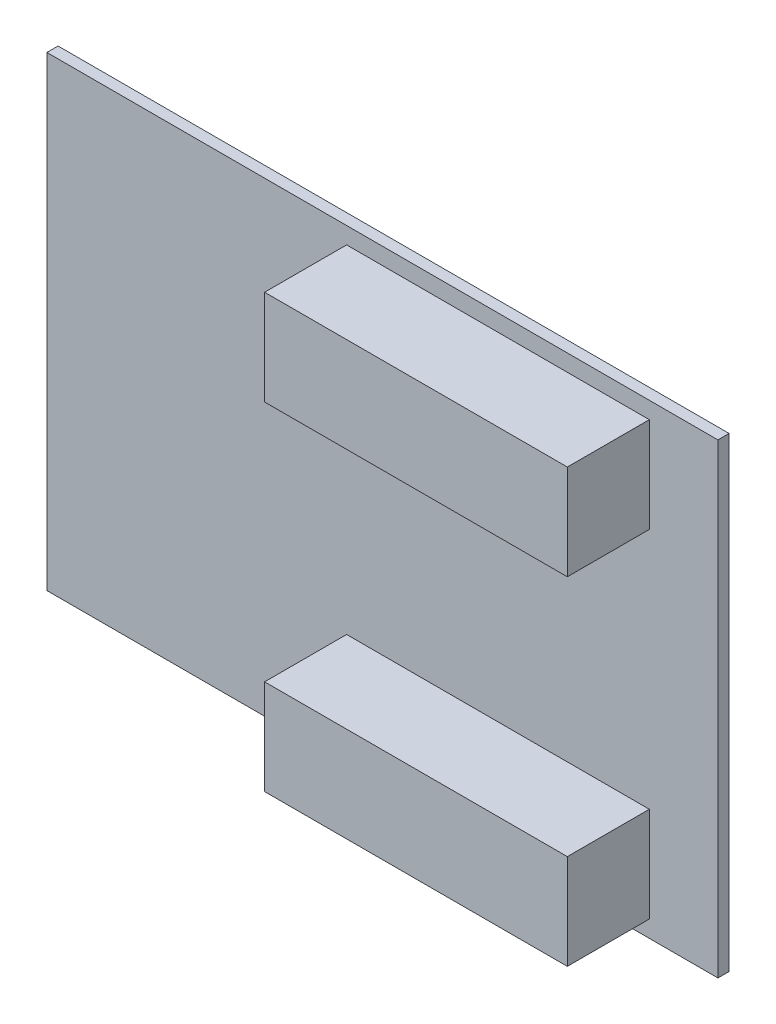
SolidWorks part; units mm, degrees
ref_plane "前视基准面" through (0, 0, 0) normal (0, 0, 1) x (1, 0, 0)
ref_plane "上视基准面" through (0, 0, 0) normal (0, 1, 0) x (1, 0, 0)
ref_plane "右视基准面" through (0, 0, 0) normal (1, 0, 0) x (0, 0, -1)
sketch "草图1" plane through (0, 0, 0) normal (0, 0, 1) x (1, 0, 0)
  line L1 (-90, 62.5) -> (90, 62.5)
  line L2 (-90, 62.5) -> (-90, -62.5)
  line L3 (-90, -62.5) -> (90, -62.5)
  line L4 (90, 62.5) -> (90, -62.5)
  line L5 (-90, 62.5) -> (90, -62.5) construction
  line L6 (-90, -62.5) -> (90, 62.5) construction
  point P0 (0, 0)
  dimension "D1" = 125
  dimension "D2" = 180
extrude "凸台-拉伸1" add sketch "草图1" along normal blind 3
sketch "草图7" plane through (0, 0, 0) normal (0, 0, -1) x (-1, 0, 0)
  line L0 (-90, 62.5) -> (90, 62.5) construction
  line L1 (-69.1, 55.5) -> (7.1, 55.5)
  line L2 (-69.1, 55.5) -> (-69.1, 35)
  line L3 (-69.1, 35) -> (7.1, 35)
  line L4 (7.1, 55.5) -> (7.1, 35)
  line L6 (-90, -62.5) -> (-90, 62.5) construction
  dimension "D1" = 20.5
  dimension "D2" = 76.2
  dimension "D3" = 7
  dimension "D4" = 20.9
extrude "电池位切除-拉伸3" cut sketch "草图7" against normal up to next
sketch "草图8" plane through (0, 0, 3) normal (0, 0, 1) x (1, 0, 0)
  line L12 (69.1, 55.5) -> (69.1, 35) construction
  line L13 (-9.6, 58) -> (71.6, 58)
  line L14 (-9.6, 58) -> (-9.6, 32.5)
  line L15 (-9.6, 32.5) -> (71.6, 32.5)
  line L16 (71.6, 58) -> (71.6, 32.5)
  line L17 (-7.1, 35) -> (-7.1, 55.5) construction
  line L18 (-7.1, 55.5) -> (69.1, 55.5) construction
  line L19 (69.1, 35) -> (-7.1, 35) construction
  line L20 (-7.1, 55.5) -> (69.1, 55.5)
  line L21 (69.1, 35) -> (-7.1, 35)
  line L22 (69.1, 55.5) -> (69.1, 35)
  line L23 (-7.1, 35) -> (-7.1, 55.5) construction
  line L24 (-7.1, 35) -> (-7.1, 55.5)
  dimension "D1" = 2.5
  dimension "D2" = 2.5
  dimension "D3" = 2.5
  dimension "D4" = 2.5
extrude "凸台-拉伸2" add sketch "草图8" along normal blind 22
sketch "草图9" plane through (0, 0, 25) normal (0, 0, 1) x (1, 0, 0)
  line L0 (71.6, 58) -> (-9.6, 58) construction
  line L5 (71.6, 58) -> (-9.6, 58)
  line L6 (-9.6, 32.5) -> (71.6, 32.5) construction
  line L7 (-9.6, 32.5) -> (71.6, 32.5)
  line L8 (71.6, 32.5) -> (71.6, 58) construction
  line L9 (71.6, 32.5) -> (71.6, 58)
  line L10 (-9.6, 58) -> (-9.6, 32.5) construction
  line L11 (-9.6, 58) -> (-9.6, 32.5)
extrude "凸台-拉伸3" add sketch "草图9" against normal blind 2.5
sketch "草图4" plane through (0, 0, 0) normal (0, 0, -1) x (-1, 0, 0)
  line L0 (7.1, 35) -> (7.1, 55.5) construction
  line L5 (7.1, 45.25) -> (84.6307, 45.25) construction
  line L10 (83.2374, -53.4277) -> (79.3374, -53.4277) construction
  line L11 (83.2374, -49.6277) -> (83.2374, -53.4277) construction
  line L12 (79.3374, -49.6277) -> (83.2374, -49.6277) construction
  line L29 (7.1, 41.25) -> (11.1, 41.25)
  line L30 (11.1, 41.25) -> (11.1, 49.25)
  line L31 (11.1, 49.25) -> (7.1, 49.25)
  line L32 (7.1, 49.25) -> (7.1, 41.25)
  dimension "D1" = 8
  dimension "D2" = 4
extrude "切除-拉伸2" cut sketch "草图4" along normal blind 1.6 from surface starting at face at (0, 0, 3)
mirror "镜向1" about plane through (0, 0, 0) normal (0, 1, 0) of "切除-拉伸2", "凸台-拉伸3", "凸台-拉伸2", "电池位切除-拉伸3"
